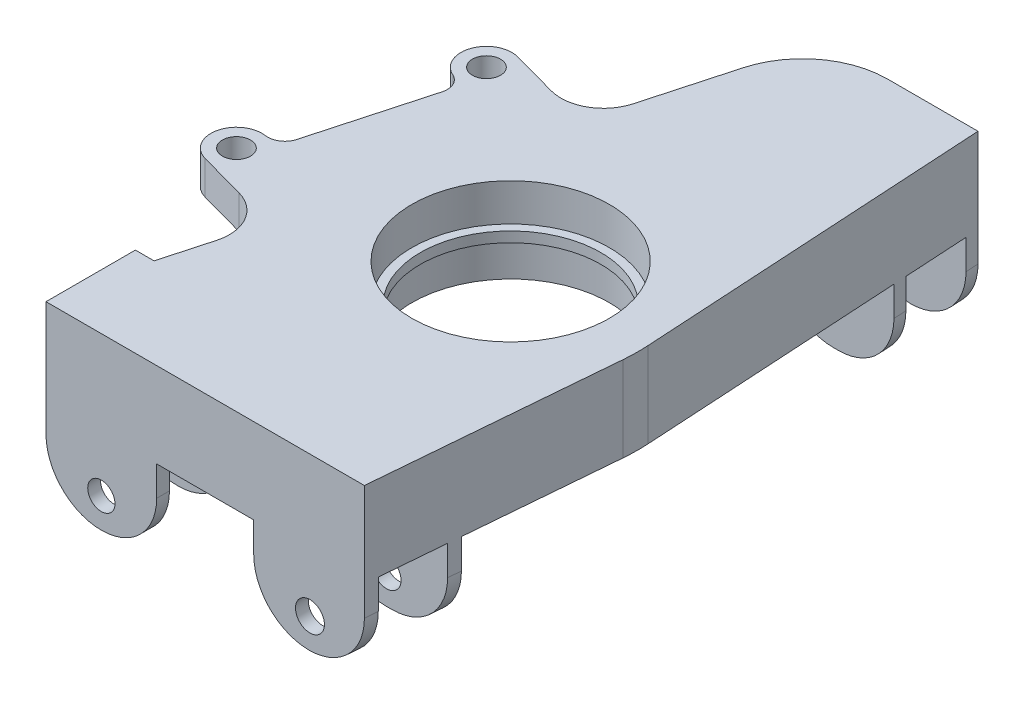
SolidWorks part; units mm, degrees
ref_plane "Front Plane" through (0, 0, 0) normal (0, 0, 1) x (1, 0, 0)
ref_plane "Top Plane" through (0, 0, 0) normal (0, 1, 0) x (1, 0, 0)
ref_plane "Right Plane" through (0, 0, 0) normal (1, 0, 0) x (0, 0, -1)
sketch "Sketch1" plane through (0, 0, 0) normal (0, 1, 0) x (1, 0, 0)
  line L0 (-58.8856, -79.7284) -> (36.1071, -79.7284)
  line L1 (42.4795, -4.9903) -> (36.1071, 103.3395)
  line L2 (36.1071, 103.3395) -> (9.1499, 103.3395)
  line L3 (-15.3365, 84.6905) -> (-53.3139, -53.0584)
  line L4 (36.1071, 103.3395) -> (36.1071, -79.7284) construction
  line L5 (36.1071, -79.7284) -> (42.4795, -4.9903)
  line L6 (-58.8856, -79.7284) -> (-58.8856, -53.0584)
  line L7 (-58.8856, -53.0584) -> (-53.3139, -53.0584)
  circle A0 centre (0, 0) radius 29.464
  circle A2 centre (0, 0) radius 120.65
  arc A3 (9.1499, 103.3395) -> (-15.3365, 84.6905) centre (9.1499, 77.9395) ccw
  point P10 (0, -29.464)
  point P11 (29.464, 0)
  point P16 (-29.464, 0)
  dimension "D2" = 58.928
  dimension "D3" = 12.7
  dimension "D4" = 8.89
  dimension "D5" = 26.67
  dimension "D1" = 241.3
  dimension "D6" = 25.4
extrude "Base" add sketch "Sketch1" along normal blind 25.4 contours L2 L3 L0 L1 A0 | L1 L4 A0 L5 region at (-56.8231, 0, 66.3934) region at (38.2312, 0, -6.2069)
sketch "Sketch2" plane through (0, 0, 0) normal (0, 1, 0) x (1, 0, 0)
  line L0 (36.1071, 103.3395) -> (36.3312, 99.5295)
  line L1 (42.4795, -4.9903) -> (36.1071, 103.3395) construction
  line L2 (36.3312, 99.5295) -> (3.0871, 99.5295)
  line L3 (3.0871, 99.5295) -> (3.0871, 103.3395)
  line L4 (36.1071, 103.3395) -> (9.1499, 103.3395) construction
  line L5 (3.0871, 103.3395) -> (36.1071, 103.3395)
  line L6 (3.0871, -75.9184) -> (36.432, -75.9184)
  line L7 (36.432, -75.9184) -> (36.1071, -79.7284)
  line L8 (-58.8856, -79.7284) -> (36.1071, -79.7284) construction
  line L9 (36.1071, -79.7284) -> (3.0871, -79.7284)
  line L10 (3.0871, -79.7284) -> (3.0871, -75.9184)
  line L11 (3.0871, 103.3395) -> (3.0871, -79.7284) construction
  line L12 (36.1071, -79.7284) -> (42.4795, -4.9903) construction
  line L13 (3.0871, 80.4795) -> (3.0871, 76.6695)
  line L14 (3.0871, 76.6695) -> (37.6759, 76.6695)
  line L15 (37.6759, 76.6695) -> (37.4518, 80.4795)
  line L16 (37.4518, 80.4795) -> (3.0871, 80.4795)
  line L17 (-58.8856, -79.7284) -> (-58.8856, -53.0584) construction
  line L18 (3.0871, -53.0584) -> (38.3811, -53.0584)
  line L19 (3.0871, -53.0584) -> (3.0871, -56.8684)
  line L20 (3.0871, -56.8684) -> (38.0562, -56.8684)
  line L21 (38.3811, -53.0584) -> (38.0562, -56.8684)
  line L22 (-25.8656, -53.0584) -> (-58.8856, -53.0584)
  line L23 (-25.8656, -53.0584) -> (-25.8656, -56.8684)
  line L24 (-25.8656, -56.8684) -> (-58.8856, -56.8684)
  line L25 (-58.8856, -53.0584) -> (-58.8856, -56.8684)
  line L26 (-25.8656, -79.7284) -> (-25.8656, -60.0458) construction
  line L27 (-58.8856, -75.9184) -> (-25.8656, -75.9184)
  line L28 (-58.8856, -75.9184) -> (-58.8856, -79.7284)
  line L29 (-58.8856, -79.7284) -> (-25.8656, -79.7284)
  line L30 (-25.8656, -75.9184) -> (-25.8656, -79.7284)
  line L31 (-58.8856, -79.7284) -> (36.1071, -79.7284) construction
  dimension "D1" = 33.02
  dimension "D2" = 3.81
  dimension "D3" = 3.81
  dimension "D4" = 19.05
  dimension "D5" = 3.81
  dimension "D6" = 3.81
  dimension "D7" = 19.05
  dimension "D8" = 33.02
  dimension "D9" = 3.81
  dimension "D10" = 3.81
extrude "A-Arms" add sketch "Sketch2" against normal blind 25.4
fillet "Fillet a-arm tab f" radius 16.51 12 edges at (36.2695, -25.4, 77.8234) (38.2186, -25.4, 54.9634) (3.0871, -25.4, 77.8234) (3.0871, -25.4, 54.9634) (37.5639, -25.4, -78.5745) (36.2192, -25.4, -101.4345) (3.0871, -25.4, -78.5745) (3.0871, -25.4, -101.4345) (-58.8856, -25.4, 77.8234) (-25.8656, -25.4, 77.8234) (-25.8656, -25.4, 54.9634) (-58.8856, -25.4, 54.9634)
fillet "Fillet2" radius 50.8 1 edges at (42.4795, 12.7, 4.9903)
ref_plane "Plane1" through (0, 1, 0) normal (0, -1, 0) x (-1, 0, 0)
sketch "Sketch3" plane through (0, 25.4, 0) normal (0, -1, 0) x (-1, 0, 0)
  line L0 (25.7961, 46.7522) -> (51.7371, 53.9041)
  line L1 (15.3365, 84.6905) -> (53.3139, -53.0584) construction
  line L2 (45.9136, -26.2164) -> (72.1885, -18.9724)
  line L3 (54.0145, 33.5988) -> (63.3923, -0.4157)
  line L4 (25.7961, 46.7522) -> (45.9136, -26.2164)
  circle A0 centre (0, 0) radius 71.12
  circle A1 centre (53.7624, 46.5582) radius 4.191
  circle A2 centre (70.1632, -11.6265) radius 4.191
  arc A3 (56.852, 39.5926) -> (51.7371, 53.9041) centre (53.7624, 46.5582) ccw
  arc A4 (72.1885, -18.9724) -> (69.039, -4.0899) centre (70.1632, -11.6265) ccw
  arc A5 (63.3923, -0.4157) -> (69.039, -4.0899) centre (68.2896, 0.9345) ccw
  arc A6 (54.0145, 33.5988) -> (56.852, 39.5926) centre (58.9118, 34.949) cw
  line M25 (15.3365, 84.6905) -> (53.3139, -53.0584)
  dimension "D1" = 60.452
  dimension "D2" = 142.24
  dimension "D3" = 8.382
  dimension "D4" = 8.382
  dimension "D5" = 15.24
  dimension "D6" = 15.24
  dimension "D7" = 5.08
extrude "Boss-Extrude3" add sketch "Sketch3" along normal blind 10 contours A6 L3 A5 A4 A0 A2 L2 L0 A1 A3 M25 | A3 A0 A1 L0 | A4 L2 A0 A2 region at (-47.6947, 25.4, -13.4368) region at (-49.7533, 25.4, -53.1565) region at (-69.0083, 25.4, 17.9571)
fillet "Fillet3" radius 12.7 2 edges at (-25.7961, 20.4, -46.7522) (-45.9136, 20.4, 26.2164)
sketch "Sketch6" plane through (0, 0, -103.3395) normal (0, 0, -1) x (-1, 0, 0)
  line L0 (-19.5828, -25.4) -> (-19.5828, 3.0923) construction
  circle A1 centre (-19.5828, -11.8937) radius 4.064
  dimension "D1" = 14.986
  dimension "D2" = 8.128
extrude "Tab Holes 1" cut sketch "Sketch6" against normal blind 38.1
sketch "Sketch7" plane through (0, 0, 53.0584) normal (0, 0, -1) x (-1, 0, 0)
  line L0 (42.3756, -25.4) -> (42.3756, 0) construction
  line L1 (25.8656, 0) -> (53.3139, 0) construction
  circle A0 centre (42.3756, -16.51) radius 4.064
  point P2 (42.3756, -15.3181)
  point P5 (42.3756, 0)
  dimension "D1" = 16.51
  dimension "D2" = 8.128
extrude "Tab Holes 2" cut sketch "Sketch7" against normal through all
ref_plane "midplane" through (0, 12.7, 0) normal (0, 1, 0) x (1, 0, 0)
sketch "Sketch8" plane through (0, 12.7, 0) normal (0, 1, 0) x (1, 0, 0)
  circle A2 centre (0, 0) radius 29.464 construction
  circle A3 centre (0, 0) radius 29.464
  circle A5 centre (0, 0) radius 26.924
  dimension "D1" = 2.54
extrude "mid-feature bearing" add sketch "Sketch8" along normal blind 1.524 and the other way blind 1.524
sketch "pushrod" plane through (0, 0, 0) normal (0, 1, 0) x (1, 0, 0)
  line L0 (-58.8856, -79.7284) -> (36.1071, -79.7284) construction
  line L1 (-32.844, -79.7284) -> (0.176, -79.7284)
  line L2 (-32.844, -79.7284) -> (-32.844, -75.9184)
  line L3 (-32.844, -75.9184) -> (0.176, -75.9184)
  line L4 (0.176, -79.7284) -> (0.176, -75.9184)
  line L5 (-45.2966, -56.8684) -> (3.0871, -56.8684) construction
  line L6 (0.176, -75.9184) -> (-3.634, -75.9184)
  line L7 (0.176, -75.9184) -> (0.176, -56.8684)
  line L8 (0.176, -56.8684) -> (-3.634, -56.8684)
  line L9 (-3.634, -75.9184) -> (-3.634, -56.8684)
  line L10 (-32.844, -75.9184) -> (-29.034, -75.9184)
  line L11 (-32.844, -75.9184) -> (-32.844, -56.8684)
  line L12 (-32.844, -56.8684) -> (-29.034, -56.8684)
  line L13 (-29.034, -75.9184) -> (-29.034, -56.8684)
  line L14 (3.0871, -53.0584) -> (3.0871, -56.8684) construction
  dimension "D1" = 3.81
  dimension "D2" = 3.81
  dimension "D3" = 3.81
  dimension "D4" = 25.4
mirror "Mirror2" [suppressed] of bodies 108
delete or keep bodies "Body-Delete/Keep 1" [suppressed] type delete bodies bodies 108
sketch "Sketch11" plane through (0, 0, 79.7284) normal (0, 0, -1) x (-1, 0, 0)
  line L0 (-19.8621, 0) -> (-19.8621, -25.4) construction
  circle A0 centre (-19.8621, -16.51) radius 4.318
  dimension "D1" = 16.51
extrude "Tab Holes 3" cut sketch "Sketch11" along normal blind 50.8
ref_plane "Plane2" through (0, 0, -90.0045) normal (0, 0, -1) x (-1, 0, 0)
ref_axis "Axis1" through (19.5828, -11.8937, -76.6695) along (0, 0, -1)
ref_point "top wishbont att pt"
ref_plane "Plane3" through (0, 0, 66.3934) normal (0, 0, -1) x (-1, 0, 0)
ref_axis "Axis2" through (19.8621, -16.51, 53.0584) along (0, 0, 1)
ref_point "Bottom Wish"
ref_axis "Axis3" through (-42.3756, -16.51, 56.8684) along (0, 0, -1)
ref_point "Anchor tierod"
